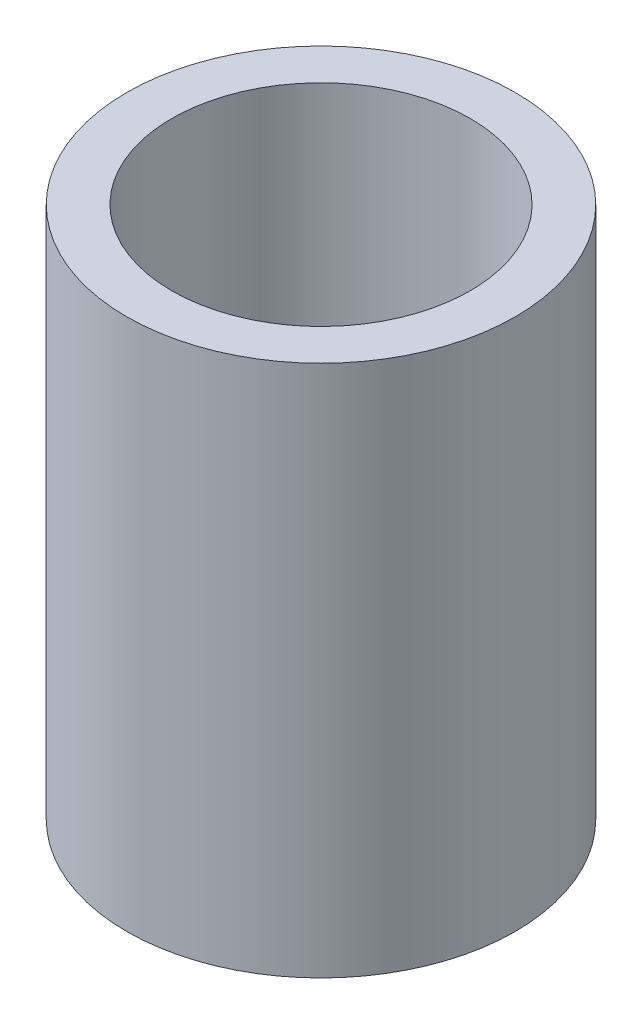
SolidWorks part; units mm, degrees
ref_plane "Front Plane" through (0, 0, 0) normal (0, 0, 1) x (1, 0, 0)
ref_plane "Top Plane" through (0, 0, 0) normal (0, 1, 0) x (1, 0, 0)
ref_plane "Right Plane" through (0, 0, 0) normal (1, 0, 0) x (0, 0, -1)
sketch "Sketch1" plane through (0, 0, 0) normal (0, 1, 0) x (1, 0, 0)
  circle A0 centre (0, 0) radius 20
  dimension "SLEEVE_OD" = 40
extrude "Boss-Extrude1" add sketch "Sketch1" along normal blind 54.8058
sketch "Sketch2" plane through (0, 0, 0) normal (0, 1, 0) x (1, 0, 0)
  circle A0 centre (0, 0) radius 15.3644
  dimension "BORE_D" = 30.7288
extrude "Cut-Extrude1" cut sketch "Sketch2" along normal through all
chamfer "Chamfer1" distance 3.3291 angle 69.525 rebuild error yes
